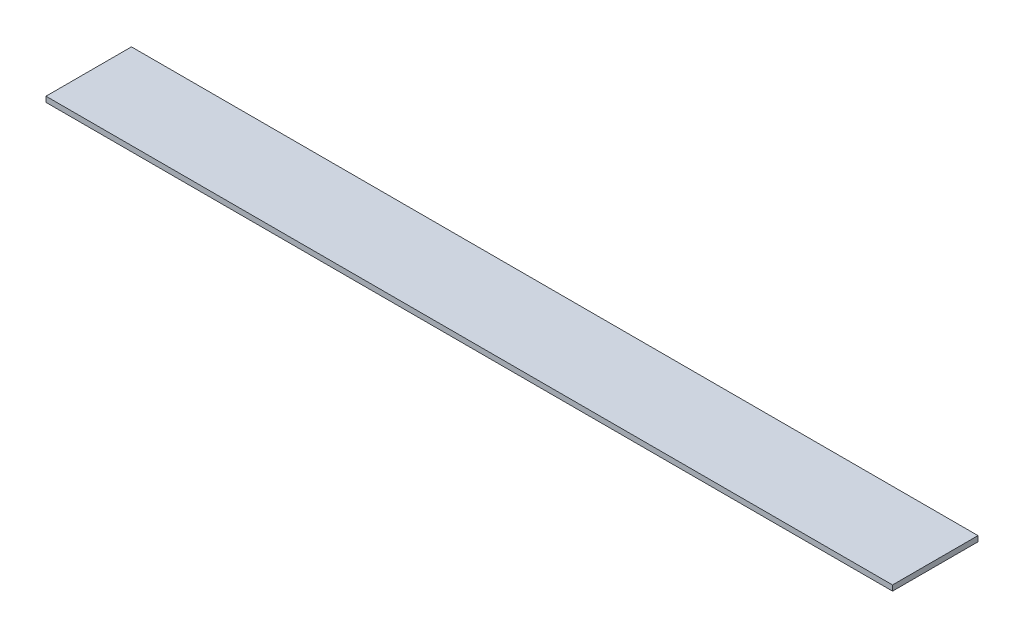
SolidWorks part; units mm, degrees
material "CK45"
ref_plane "Front Plane" through (0, 0, 0) normal (0, 0, 1) x (1, 0, 0)
ref_plane "Top Plane" through (0, 0, 0) normal (0, 1, 0) x (1, 0, 0)
ref_plane "Right Plane" through (0, 0, 0) normal (1, 0, 0) x (0, 0, -1)
sketch "Sketch1" plane through (0, 0, 0) normal (0, 1, 0) x (1, 0, 0)
  line L1 (-940, -94.9) -> (940, -94.9)
  line L2 (-940, -94.9) -> (-940, 94.9)
  line L3 (-940, 94.9) -> (940, 94.9)
  line L4 (940, -94.9) -> (940, 94.9)
  line L5 (-940, -94.9) -> (940, 94.9) construction
  line L6 (-940, 94.9) -> (940, -94.9) construction
  point P0 (0, 0)
  dimension "D1" = 1880
  dimension "1" = 189.8
base flange "Base-Flange1" sketch "Sketch1" thickness 12 reverse thickness direction no parameters "D1"=15
sketch "Bend-Lines1" [suppressed] plane through (0, 0, 0) normal (0, 1, 0) x (1, 0, 0)
sketch "Bounding-Box1" [suppressed] plane through (0, 0, 0) normal (0, 1, 0) x (1, 0, 0)
sheet metal parameters "Sheet-Metal2" thickness 12 parameters "D1"=3
flat pattern "Flat-Pattern2" [suppressed]
sketch "Bend-Lines2" plane through (0, 0, 0) normal (0, 1, 0) x (1, 0, 0)
sketch3d "Bounding-Box2" [suppressed]
  line L0 (940, 94.9, 0) -> (-940, 94.9, 0) construction
  line L1 (940, -94.9, 0) -> (-940, -94.9, 0) construction
  line L2 (940, 94.9, 0) -> (940, -94.9, 0) construction
  line L3 (-940, 94.9, 0) -> (-940, -94.9, 0) construction
